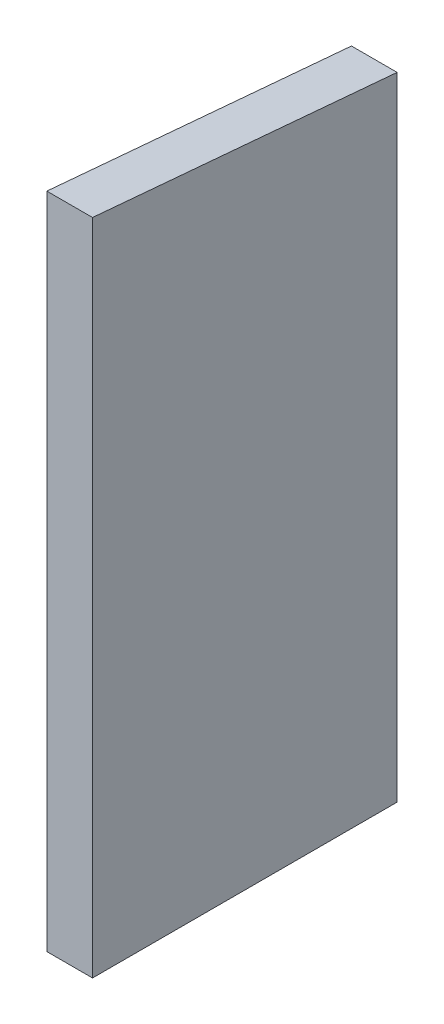
SolidWorks part; units mm, degrees
material "Cedro"
ref_plane "Alzado" through (0, 0, 0) normal (0, 0, 1) x (1, 0, 0)
ref_plane "Planta" through (0, 0, 0) normal (0, 1, 0) x (1, 0, 0)
ref_plane "Vista lateral" through (0, 0, 0) normal (1, 0, 0) x (0, 0, -1)
sketch "Croquis1" plane through (0, 0, 0) normal (0, 1, 0) x (1, 0, 0)
  line L1 (-7.5, -50) -> (7.5, -50)
  line L2 (-7.5, -50) -> (-7.5, 50)
  line L3 (-7.5, 50) -> (7.5, 50)
  line L4 (7.5, -50) -> (7.5, 50)
  line L5 (-7.5, -50) -> (7.5, 50) construction
  line L6 (-7.5, 50) -> (7.5, -50) construction
  point P0 (0, 0)
  dimension "D1" = 15
  dimension "D2" = 100
extrude "Saliente-Extruir1" add sketch "Croquis1" along normal blind 250
sketch "Croquis2" plane through (7.5, 0, 0) normal (1, 0, 0) x (0, 0, -1)
  line L0 (-50, 216.2023) -> (50, 207.4535)
  line L1 (-50, 250) -> (-50, 0) construction
  line L2 (-251.75, 233.8532) -> (-79.5053, 218.7837) construction
  line L3 (50, 250) -> (50, 0) construction
  line L4 (50, 207.4535) -> (50, 250)
  line L5 (50, 250) -> (-50, 250)
  line L6 (-50, 250) -> (-50, 216.2023)
  dimension "D1" = 95
extrude "Cortar-Extruir1" cut sketch "Croquis2" against normal through all
